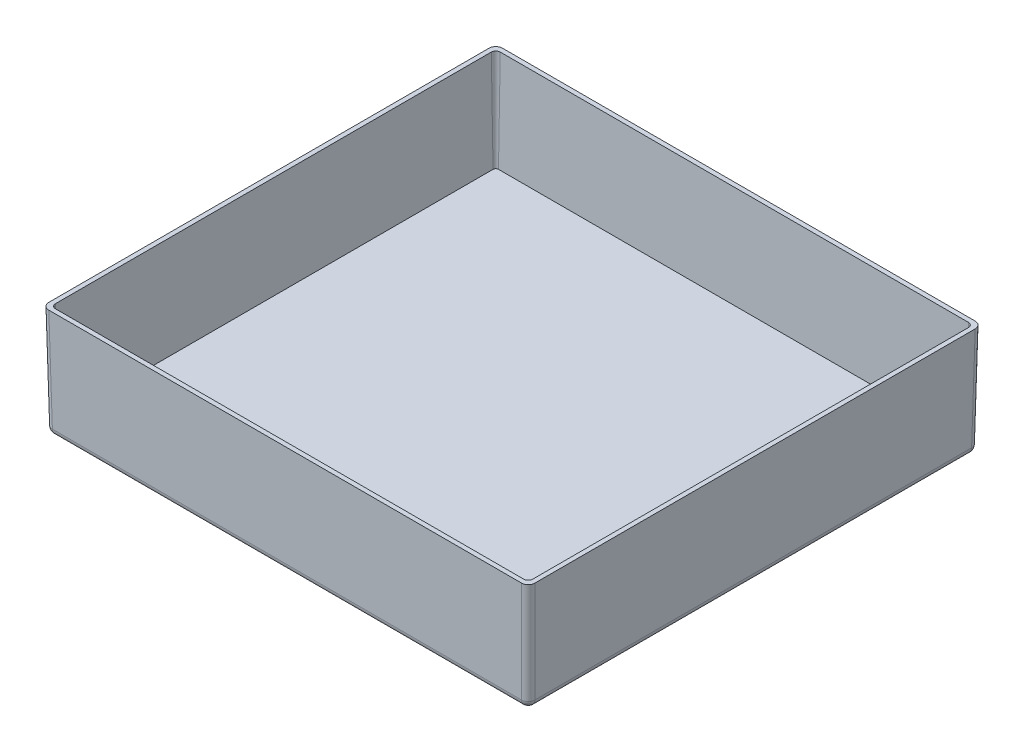
SolidWorks part; units mm, degrees
ref_plane "Front Plane" through (0, 0, 0) normal (0, 0, 1) x (1, 0, 0)
ref_plane "Top Plane" through (0, 0, 0) normal (0, 1, 0) x (1, 0, 0)
ref_plane "Right Plane" through (0, 0, 0) normal (1, 0, 0) x (0, 0, -1)
ref_axis "Axis1" through (-33.0333, 0, 0) along (1, 0, 0)
ref_axis "Axis2" through (0, 24.5224, 0) along (0, -1, 0)
ref_axis "Axis3" through (0, 0, -30.7663) along (0, 0, 1)
sketch "Sketch1" plane through (0, 0, 0) normal (0, 1, 0) x (1, 0, 0)
  line L1 (-107.75, -100.5) -> (107.75, -100.5)
  line L2 (-107.75, -100.5) -> (-107.75, 100.5)
  line L3 (-107.75, 100.5) -> (107.75, 100.5)
  line L4 (107.75, -100.5) -> (107.75, 100.5)
  line L5 (-107.75, -100.5) -> (107.75, 100.5) construction
  line L6 (-107.75, 100.5) -> (107.75, -100.5) construction
  point P0 (0, 0)
  dimension "D1" = 215.5
  dimension "D2" = 201
extrude "Boss-Extrude1" add sketch "Sketch1" along normal blind 49 draft 1 draft outward yes
fillet "Fillet1" radius 3 8 edges at (0, 0, -100.5) (-108.1776, 24.5, -100.9276) (108.1776, 24.5, -100.9276) (107.75, 0, 0) (108.1776, 24.5, 100.9276) (-107.75, 0, 0) (0, 0, 100.5) (-108.1776, 24.5, 100.9276)
sketch "Sketch2" plane through (0, 49, 0) normal (0, 1, 0) x (1, 0, 0)
  line L0 (-108.6053, 98.3558) -> (-108.6053, -98.3558) construction
  line L1 (-104.6053, -99.3553) -> (104.6053, -99.3553)
  line L2 (-106.6053, -97.3553) -> (-106.6053, 97.3553)
  line L3 (-104.6053, 99.3553) -> (104.6053, 99.3553)
  line L4 (106.6053, -97.3553) -> (106.6053, 97.3553)
  line L5 (-106.6053, -99.3553) -> (106.6053, 99.3553) construction
  line L6 (-106.6053, 99.3553) -> (106.6053, -99.3553) construction
  line L7 (105.6058, 101.3553) -> (-105.6058, 101.3553) construction
  arc A0 (-104.6053, -99.3553) -> (-106.6053, -97.3553) centre (-104.6053, -97.3553) cw
  arc A1 (104.6053, -99.3553) -> (106.6053, -97.3553) centre (104.6053, -97.3553) ccw
  arc A2 (104.6053, 99.3553) -> (106.6053, 97.3553) centre (104.6053, 97.3553) cw
  arc A3 (-106.6053, 97.3553) -> (-104.6053, 99.3553) centre (-104.6053, 97.3553) cw
  point P0 (0, 0)
  dimension "D3" = 2
  dimension "D1" = 2
  dimension "D2" = 2
extrude "Cut-Extrude1" cut sketch "Sketch2" against normal blind 45 draft 1
